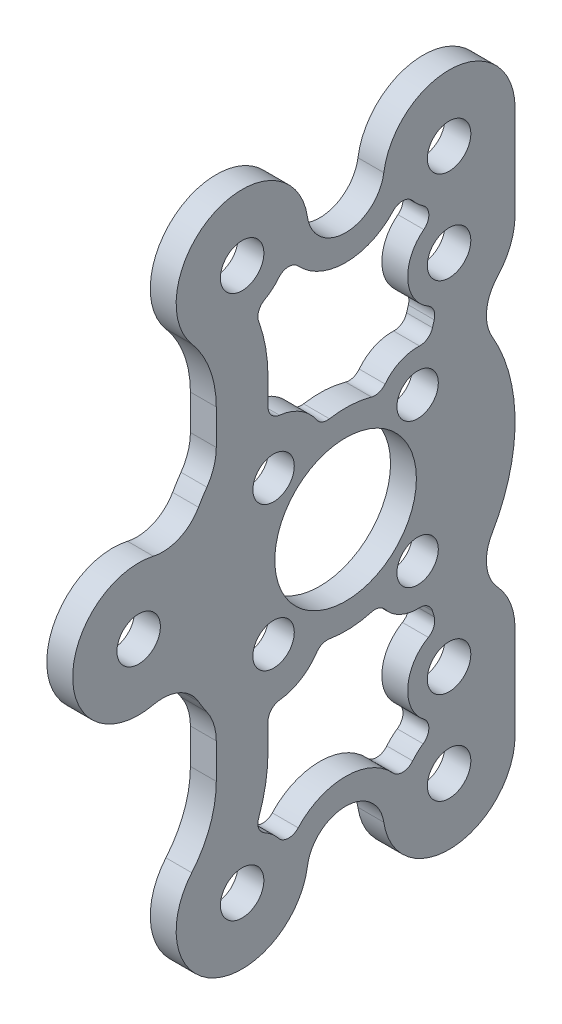
SolidWorks part; units mm, degrees
material "AR500"
ref_plane "Front Plane" through (0, 0, 0) normal (0, 0, 1) x (1, 0, 0)
ref_plane "Top Plane" through (0, 0, 0) normal (0, 1, 0) x (1, 0, 0)
ref_plane "Right Plane" through (0, 0, 0) normal (1, 0, 0) x (0, 0, -1)
ref_plane "Motor Front Plane" through (39.075, 0, 0) normal (1, 0, 0) x (0, 0, -1)
sketch "Sketch1" plane through (39.075, 0, 0) normal (1, 0, 0) x (0, 0, -1)
  line L1 (12.7, 21.997) -> (-25.4, 0) construction
  line L3 (12.7, 21.997) -> (12.7, -21.997) construction
  line L4 (-25.4, 0) -> (12.7, -21.997) construction
  line L5 (20.8, 21.997) -> (20.8, 32.6221) construction
  circle A0 centre (8.8388, -8.8388) radius 1.65 construction
  circle A1 centre (8.8388, 8.8388) radius 1.65 construction
  circle A2 centre (-8.8388, -8.8388) radius 1.65 construction
  circle A3 centre (-8.8388, 8.8388) radius 1.65 construction
  circle A4 centre (8.8388, -8.8388) radius 1.65 construction
  circle A5 centre (8.8388, 8.8388) radius 1.65 construction
  circle A6 centre (-8.8388, -8.8388) radius 1.65 construction
  circle A7 centre (-8.8388, 8.8388) radius 1.65 construction
  circle A8 centre (0, 0) radius 20.8 construction
  circle A9 centre (0, 0) radius 8.69
  circle A10 centre (-8.8388, 8.8388) radius 2.54
  circle A11 centre (8.8388, 8.8388) radius 2.54
  circle A12 centre (8.8388, -8.8388) radius 2.54
  circle A13 centre (-8.8388, -8.8388) radius 2.54
  circle A14 centre (-8.8388, 8.8388) radius 3.81 construction
  circle A16 centre (12.7, 21.997) radius 2.667
  circle A18 centre (12.7, -21.997) radius 2.667
  circle A19 centre (-25.4, 0) radius 2.667
  arc A20 (-19.925, -5.9695) -> (4.7928, -20.2403) centre (0, 0) ccw
  arc A21 (-19.925, 5.9695) -> (4.7928, 20.2403) centre (0, 0) cw
  arc A23 (15.1322, 14.2708) -> (15.1322, -14.2708) centre (0, 0) cw
  arc A24 (-19.925, -5.9695) -> (-19.925, 5.9695) centre (-25.4, 0) cw
  arc A25 (4.7928, 20.2403) -> (15.1322, 14.2708) centre (12.7, 21.997) cw
  arc A27 (4.7928, -20.2403) -> (15.1322, -14.2708) centre (12.7, -21.997) ccw
  circle A28 centre (0, 0) radius 25.4 construction
  dimension "D1" = 41.6
  dimension "D2" = 5.08
  dimension "D3" = 7.62
  dimension "D4" = 5.334
  dimension "D5" = 50.8
extrude "Boss-Extrude1" add sketch "Sketch1" along normal blind 3.175
fillet "Fillet1" radius 5.08 6 edges at (40.6625, 5.9695, 19.925) (40.6625, -14.2708, -15.1322) (40.6625, -20.2403, -4.7928) (40.6625, -5.9695, 19.925) (40.6625, 20.2403, -4.7928) (40.6625, 14.2708, -15.1322)
sketch "Sketch2" plane through (42.25, 0, 0) normal (1, 0, 0) x (0, 0, -1)
  line L0 (-12.7, -33.3375) -> (-12.7, 33.3375) construction
  line L5 (0, 0) -> (-12.7, 0) construction
  line L6 (0, 0) -> (0, 30.48) construction
  line L11 (12.7, 33.3375) -> (12.7, 21.997) construction
  line L13 (20.8, 33.3375) -> (20.8, 21.997)
  line L14 (-15.875, 19.8978) -> (-15.875, 13.4397)
  line L15 (11.7095, 24.4733) -> (-15.875, 13.4397)
  arc A24 (-4.6874, 34.5243) -> (-18.8821, 28.1038) centre (-12.7, 33.3375) ccw
  circle A27 centre (-12.7, 33.3375) radius 2.667
  circle A32 centre (12.7, 33.3375) radius 2.667
  arc A33 (4.6874, 34.5243) -> (20.8, 33.3375) centre (12.7, 33.3375) cw
  circle A34 centre (-25.4, 0) radius 2.667 construction
  arc A35 (-4.6874, 34.5243) -> (4.6874, 34.5243) centre (0, 35.2185) ccw
  arc A39 (18.6368, 16.4866) -> (4.9595, 24.3833) centre (12.7, 21.997) ccw construction
  arc A40 (-18.8821, 28.1038) -> (-15.875, 19.8978) centre (-28.575, 19.8978) cw
  arc A41 (0.0843, 20.7998) -> (-18.0553, 10.3269) centre (0, 0) ccw construction
  arc A42 (20.8, 21.997) -> (11.7095, 24.4733) centre (14.614, 17.2119) ccw
  circle A43 centre (12.7, 21.997) radius 2.667 construction
  dimension "D3" = 30.48
  dimension "D1" = 6.35
  dimension "D4" = 12.7
  dimension "D2" = 66.675
extrude "Boss-Extrude2" add sketch "Sketch2" against normal up to surface (3.175 mm away) up to face at (39.075, -21.997, -15.367)
sketch "Sketch3" plane through (39.075, 0, 0) normal (-1, 0, 0) x (0, 0, 1)
  line L0 (-11.2696, 17.1226) -> (-10.2692, 13.7133)
  line L1 (-12.7, 33.3375) -> (-12.7, 21.997)
  line L2 (9.525, 15.1517) -> (9.525, 19.8978)
  line L3 (15.875, 19.8978) -> (15.875, 13.4397) construction
  circle A0 centre (-12.7, 21.997) radius 5.08
  circle A1 centre (-8.8388, 8.8388) radius 5.08
  circle A2 centre (8.8388, 8.8388) radius 6.35
  circle A3 centre (12.7, 33.3375) radius 5.715
  circle A4 centre (-12.7, 33.3375) radius 5.715
  arc A5 (-7.1743, 31.8788) -> (7.1743, 31.8788) centre (0, 35.2185) ccw
  arc A6 (-4.6874, 34.5243) -> (4.6874, 34.5243) centre (0, 35.2185) ccw construction
  arc A7 (-9.5127, 28.5938) -> (-9.597, 26.0192) centre (-8.6273, 27.2762) ccw
  circle A8 centre (0, 0) radius 11.865
  circle A9 centre (0, 0) radius 8.69 construction
  arc A10 (9.525, 19.8978) -> (11.2461, 27.8105) centre (28.575, 19.8978) cw
  arc A11 (18.8821, 28.1038) -> (15.875, 19.8978) centre (28.575, 19.8978) ccw construction
  point P38 (0, 0)
  point P39 (0, 0)
  point P40 (12.1178, 27.2762)
  dimension "D1" = 11.43
  dimension "D2" = 10.16
  dimension "D3" = 3.175
  dimension "D4" = 1.5875
  dimension "D5" = 3.175
  dimension "D7" = 12.7
  dimension "D6" = 6.35
extrude "Cut-Extrude1" cut sketch "Sketch3" against normal through all contours L2 A10 A3 A5 A4 A7 A0 L0 A1 A8 A2 region at (39.075, 20.9217, 0.0796)
fillet "Fillet3" radius 1.5875 8 edges at (40.6625, 11.4644, 3.0571) (40.6625, 11.0684, -4.2742) (40.6625, 13.7133, -10.2692) (40.6625, 17.1226, -11.2696) (40.6625, 31.8788, 7.1743) (40.6625, 27.8105, 11.2461) (40.6625, 15.1517, 9.525) (40.6625, 31.8788, -7.1743)
mirror "Mirror1" about plane through (0, 0, 0) normal (0, 1, 0) of "Cut-Extrude1", "Fillet3", "Boss-Extrude2"
fillet "Fillet2" radius 6.35 2 edges at (40.6625, -13.4397, 15.875) (40.6625, 13.4397, 15.875)
equation "\"D1@Sketch1\"=41.6mm"
